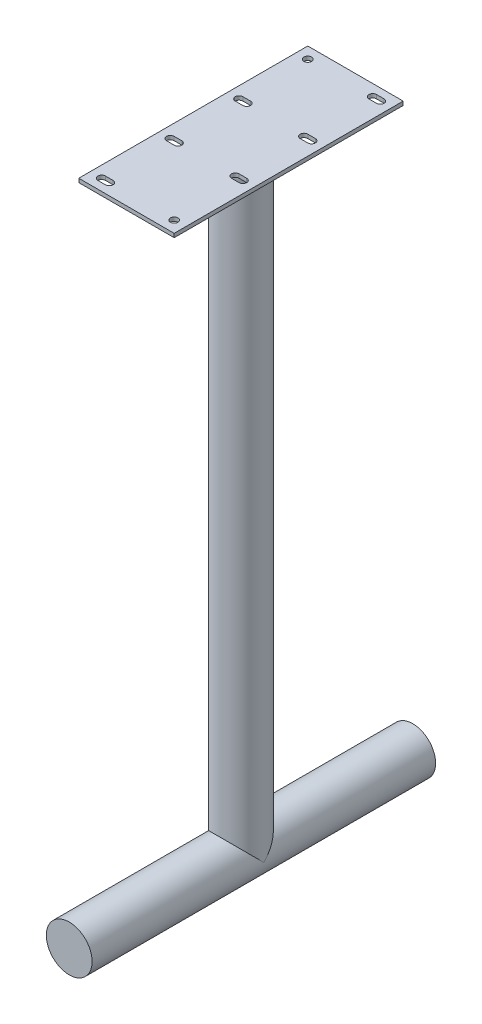
SolidWorks part; units mm, degrees
ref_plane "Front Plane" through (0, 0, 0) normal (0, 0, 1) x (1, 0, 0)
ref_plane "Top Plane" through (0, 0, 0) normal (0, 1, 0) x (1, 0, 0)
ref_plane "Right Plane" through (0, 0, 0) normal (1, 0, 0) x (0, 0, -1)
sketch "Sketch1" plane through (0, 0, 0) normal (0, 1, 0) x (1, 0, 0)
  line L0 (-47.5, 135) -> (-47.5, 45) construction
  line L1 (-62.5, -150) -> (62.5, -150)
  line L2 (-62.5, -150) -> (-62.5, 150)
  line L3 (-62.5, 150) -> (62.5, 150)
  line L4 (62.5, -150) -> (62.5, 150)
  line L5 (0, 150) -> (0, -150) construction
  line L6 (-62.5, 0) -> (62.5, 0) construction
  line L7 (-47.5, -45) -> (-47.5, -135) construction
  line L8 (-47.5, 45) -> (-47.5, -45) construction
  line L9 (-47.5, 45) -> (-37.5, 45) construction
  line L10 (-47.5, 50) -> (-37.5, 50)
  line L11 (-47.5, 40) -> (-37.5, 40)
  line L12 (-47.5, -45) -> (-37.5, -45) construction
  line L13 (-47.5, -40) -> (-37.5, -40)
  line L14 (-47.5, -50) -> (-37.5, -50)
  line L15 (-47.5, -135) -> (-37.5, -135) construction
  line L16 (-47.5, -130) -> (-37.5, -130)
  line L17 (-47.5, -140) -> (-37.5, -140)
  line L18 (47.5, -45) -> (37.5, -45) construction
  line L19 (47.5, -50) -> (37.5, -50)
  line L20 (47.5, -40) -> (37.5, -40)
  line L21 (47.5, 45) -> (37.5, 45) construction
  line L22 (47.5, 40) -> (37.5, 40)
  line L23 (47.5, 50) -> (37.5, 50)
  line L24 (47.5, 135) -> (37.5, 135) construction
  line L25 (47.5, 130) -> (37.5, 130)
  line L26 (47.5, 140) -> (37.5, 140)
  circle A0 centre (-47.5, 135) radius 5
  arc A1 (-47.5, 50) -> (-47.5, 40) centre (-47.5, 45) ccw
  arc A2 (-37.5, 40) -> (-37.5, 50) centre (-37.5, 45) ccw
  arc A3 (-47.5, -40) -> (-47.5, -50) centre (-47.5, -45) ccw
  arc A4 (-37.5, -50) -> (-37.5, -40) centre (-37.5, -45) ccw
  arc A5 (-47.5, -130) -> (-47.5, -140) centre (-47.5, -135) ccw
  arc A6 (-37.5, -140) -> (-37.5, -130) centre (-37.5, -135) ccw
  circle A8 centre (47.5, -135) radius 5
  arc A9 (47.5, -50) -> (47.5, -40) centre (47.5, -45) ccw
  arc A10 (37.5, -40) -> (37.5, -50) centre (37.5, -45) ccw
  arc A11 (47.5, 40) -> (47.5, 50) centre (47.5, 45) ccw
  arc A12 (37.5, 50) -> (37.5, 40) centre (37.5, 45) ccw
  arc A13 (47.5, 130) -> (47.5, 140) centre (47.5, 135) ccw
  arc A14 (37.5, 140) -> (37.5, 130) centre (37.5, 135) ccw
  point P0 (0, 0)
  point P6 (-42.5, 45)
  point P15 (-42.5, -45)
  point P21 (-42.5, -135)
  point P27 (93.2976, -135)
  point P28 (0, 0)
  point P29 (47.4951, -135)
  point P32 (42.5, -45)
  point P41 (42.5, 45)
  point P47 (42.5, 135)
  point P53 (0, 0)
  dimension "D5" = 10
  dimension "D7" = 2
  dimension "D1" = 300
  dimension "D2" = 125
  dimension "D3" = 90
  dimension "D4" = 15
  dimension "D6" = 10
extrude "Boss-Extrude1" add sketch "Sketch1" against normal blind 5 contours L1 L4 L3 L2 A14 L26 A13 L25 A12 L23 A11 L22 A10 L20 A9 L19 A8 A6 L17 A5 L16 A4 L14 A3 L13 A2 L11 A1 L10 A0 region at (0, 0, 0)
sketch "Sketch2" plane through (0, -5, 0) normal (0, -1, 0) x (-1, 0, 0)
  circle A0 centre (0, 0) radius 30
  dimension "D1" = 60
extrude "Boss-Extrude2" add sketch "Sketch2" along normal blind 800
sketch "Sketch3" plane through (0, 0, 0) normal (0, 0, 1) x (1, 0, 0)
  line L0 (-30, -805) -> (30, -805) construction
  circle A0 centre (0, -805) radius 30
extrude "Boss-Extrude3" add sketch "Sketch3" along normal mid plane 450
